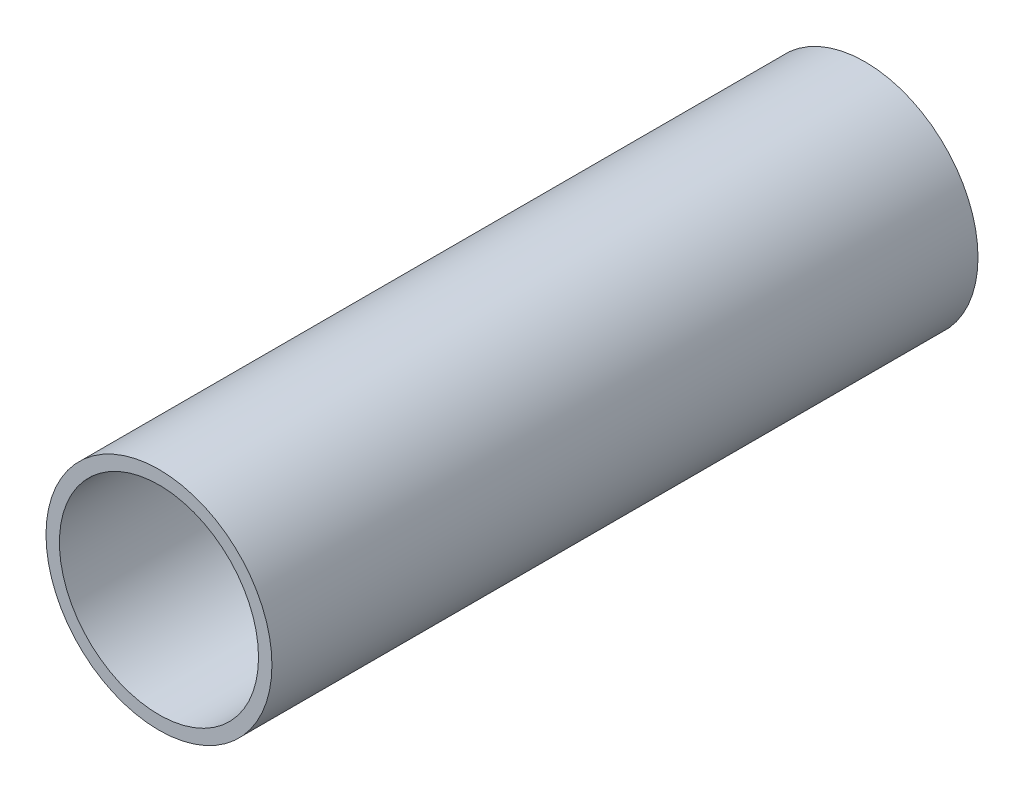
SolidWorks part; units mm, degrees
material "PE Высокой плотности"
ref_plane "Front" through (0, 0, 0) normal (0, 0, 1) x (1, 0, 0)
ref_plane "Top" through (0, 0, 0) normal (0, 1, 0) x (1, 0, 0)
ref_plane "Side" through (0, 0, 0) normal (1, 0, 0) x (0, 0, -1)
sketch "PipeSketch" plane through (0, 0, 0) normal (0, 0, 1) x (1, 0, 0)
  circle A0 centre (0, 0) radius 16
  circle A1 centre (0, 0) radius 14.1
  dimension "OuterDiameter" = 32
  dimension "InnerDiameter" = 28.2
extrude "Extrusion" add sketch "PipeSketch" along normal blind 100
sketch "FilterSketch" plane through (0, 0, 0) normal (0, 0, 1) x (1, 0, 0)
  circle A0 centre (0, 0) radius 16 construction
  dimension "NominalDiameter" = 32
